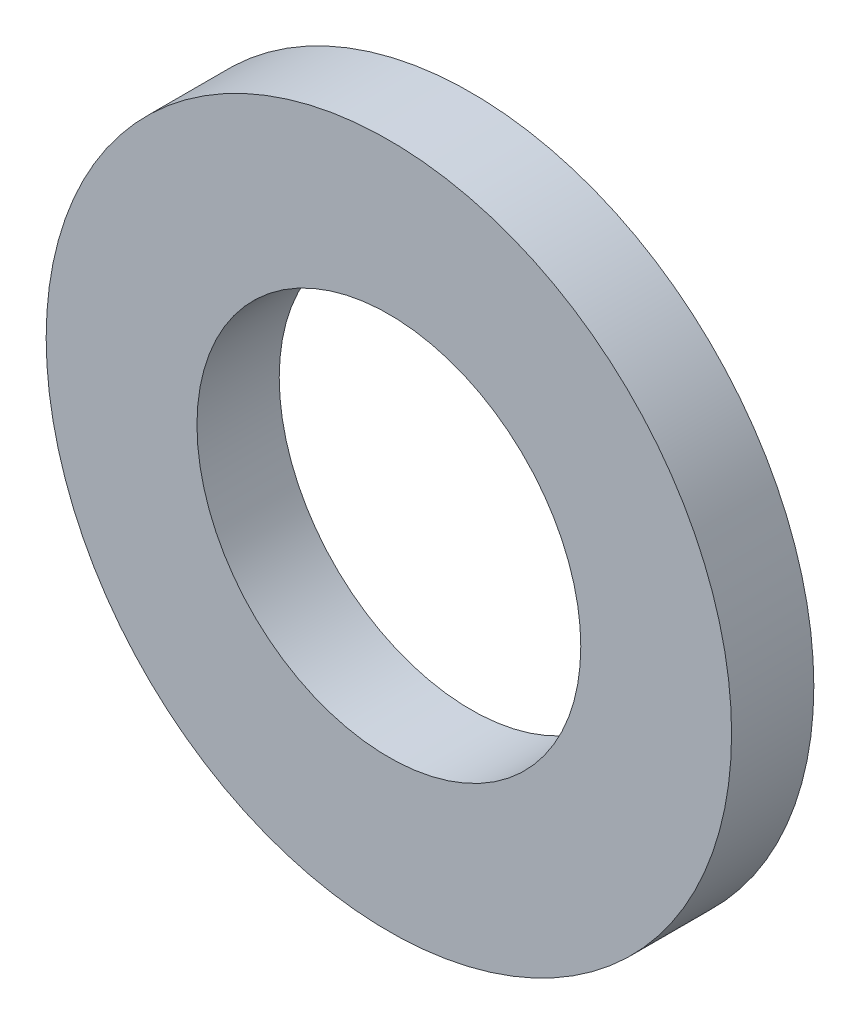
SolidWorks part; units mm, degrees
material "AISI 304"
ref_plane "Front Plane" through (0, 0, 0) normal (0, 0, 1) x (1, 0, 0)
ref_plane "Top Plane" through (0, 0, 0) normal (0, 1, 0) x (1, 0, 0)
ref_plane "Right Plane" through (0, 0, 0) normal (1, 0, 0) x (0, 0, -1)
sketch "Sketch1" plane through (0, 0, 0) normal (0, 0, 1) x (1, 0, 0)
  circle A0 centre (0, 0) radius 7.5
  circle A1 centre (0, 0) radius 4.2
  dimension "OD" = 15
  dimension "ID1" = 8.4
extrude "Boss-Extrude1" add sketch "Sketch1" along normal blind 1.8
ref_axis "Center Axis 1" through (0, 0, 1.8) along (0, 0, -1)
ref_plane "Contact Plane 1" through (0, 0, 1.8) normal (0, 0, 1) x (1, 0, 0)
ref_plane "Contact Plane 2" through (0, 0, 0) normal (0, 0, -1) x (-1, 0, 0)
